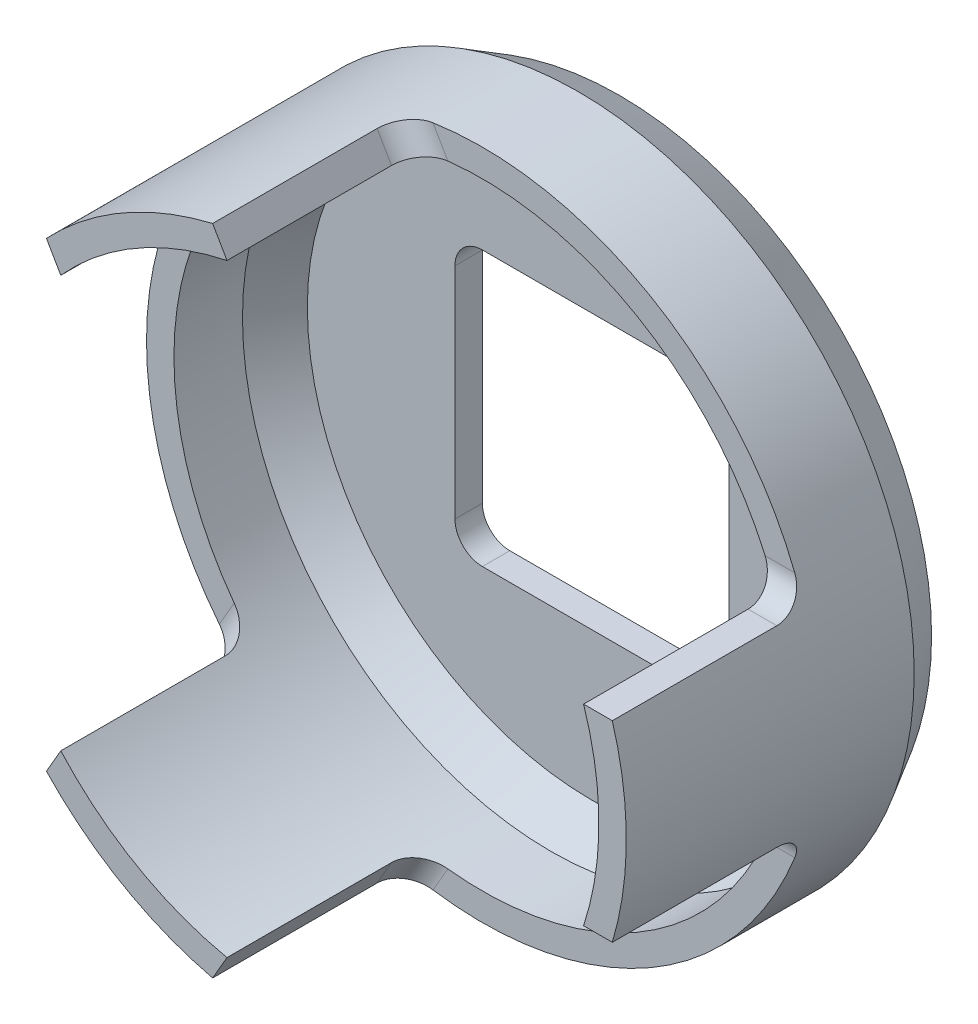
SolidWorks part; units mm, degrees
ref_plane "前视基准面" through (0, 0, 0) normal (0, 0, 1) x (1, 0, 0)
ref_plane "上视基准面" through (0, 0, 0) normal (0, 1, 0) x (1, 0, 0)
ref_plane "右视基准面" through (0, 0, 0) normal (1, 0, 0) x (0, 0, -1)
other "Configuration Table"
sketch "草图1" plane through (0, 0, 0) normal (0, 0, 1) x (1, 0, 0)
  line L1 (-10, 10) -> (10, 10)
  line L2 (-10, 10) -> (-10, -10)
  line L3 (-10, -10) -> (10, -10)
  line L4 (10, 10) -> (10, -10)
  line L5 (-10, 10) -> (10, -10) construction
  line L6 (-10, -10) -> (10, 10) construction
  circle A0 centre (0, 0) radius 24.5
  point P7 (0, 0)
  point P8 (0, 0)
  dimension "D1" = 49
  dimension "D2" = 20
extrude "凸台-拉伸1" add sketch "草图1" along normal blind 2
sketch "草图2" plane through (0, 0, 2) normal (0, 0, 1) x (1, 0, 0)
  circle A0 centre (0, 0) radius 22.5
  circle A1 centre (0, 0) radius 24.5 construction
  circle A2 centre (0, 0) radius 24.5
  dimension "D1" = 2
extrude "凸台-拉伸2" add sketch "草图2" along normal blind 8
fillet "圆角1" radius 2 4 edges at (-10, 10, 1) (10, 10, 1) (10, -10, 1) (-10, -10, 1)
sketch "草图3" plane through (0, 0, 10) normal (0, 0, 1) x (1, 0, 0)
  line L0 (0, 0) -> (24.5, 0) construction
  line L1 (23.4787, 7) -> (21.3834, 7)
  line L2 (21.3834, -7) -> (23.4787, -7)
  circle A0 centre (0, 0) radius 24.5 construction
  circle A1 centre (0, 0) radius 22.5 construction
  circle A2 centre (0, 0) radius 22.5 construction
  arc A3 (23.4787, -7) -> (23.4787, 7) centre (0, 0) ccw
  arc A4 (21.3834, -7) -> (21.3834, 7) centre (0, 0) ccw
  dimension "D1" = 14
extrude "凸台-拉伸3" add sketch "草图3" along normal blind 14
chamfer "倒角1" distance 3 angle 30 2 edges at (24.5, 0, 0) (22.5, 0, 2)
pattern_circular "阵列(圆周)2" count 3 over 360 about axis through (0, 0, 0) along (0, 0, 1) of "凸台-拉伸3"
fillet "圆角2" radius 2 6 edges at (22.4311, -7, 10) (-5.1534, -22.9259, 10) (22.4311, 7, 10) (-17.2777, -15.9259, 10) (-5.1534, 22.9259, 10) (-17.2777, 15.9259, 10)
